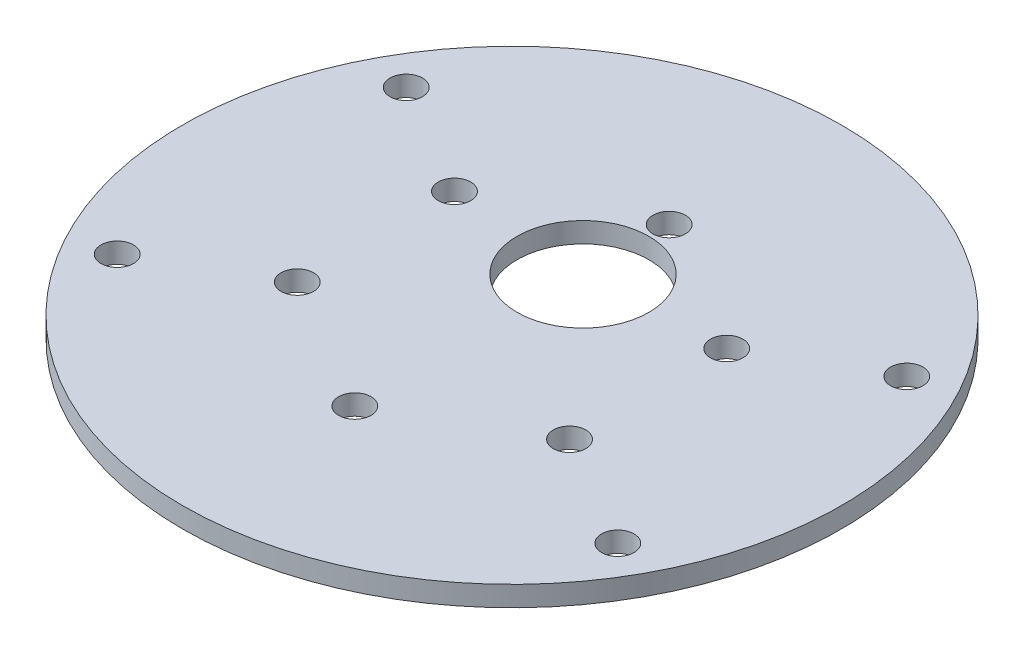
SolidWorks part; units mm, degrees
ref_plane "前视基准面" through (0, 0, 0) normal (0, 0, 1) x (1, 0, 0)
ref_plane "上视基准面" through (0, 0, 0) normal (0, 1, 0) x (1, 0, 0)
ref_plane "右视基准面" through (0, 0, 0) normal (1, 0, 0) x (0, 0, -1)
sketch "草图1" plane through (0, 0, 0) normal (0, 1, 0) x (1, 0, 0)
  line L0 (0, 0) -> (28.1458, -16.25) construction
  line L1 (0, 0) -> (32.5, 0) construction
  line L2 (0, 0) -> (0, -32.5) construction
  circle A0 centre (0, 0) radius 32.5
  circle A2 centre (-24.6817, -14.25) radius 1.6
  circle A3 centre (0, 7) radius 6.5
  circle A4 centre (24.6817, 14.25) radius 1.6
  circle A5 centre (0, 15.5) radius 1.6
  circle A6 centre (13.4234, 7.75) radius 1.6
  circle A7 centre (13.4234, -7.75) radius 1.6
  circle A8 centre (0, -15.5) radius 1.6
  circle A9 centre (-13.4234, -7.75) radius 1.6
  circle A10 centre (-13.4234, 7.75) radius 1.6
  circle A11 centre (0, 7) radius 6 construction
  circle A12 centre (24.6817, -14.25) radius 1.6
  circle A13 centre (-24.6817, 14.25) radius 1.6
  point P23 (0, 0)
  point P26 (24.6817, -14.25)
  point P35 (0, 0)
  dimension "D1" = 0.5
  dimension "D2" = 65
  dimension "D3" = 3.2
  dimension "D6" = 3.2
  dimension "D5" = 30
  dimension "D7" = 4
  dimension "D4" = 6
extrude "凸台-拉伸1" add sketch "草图1" along normal blind 2
